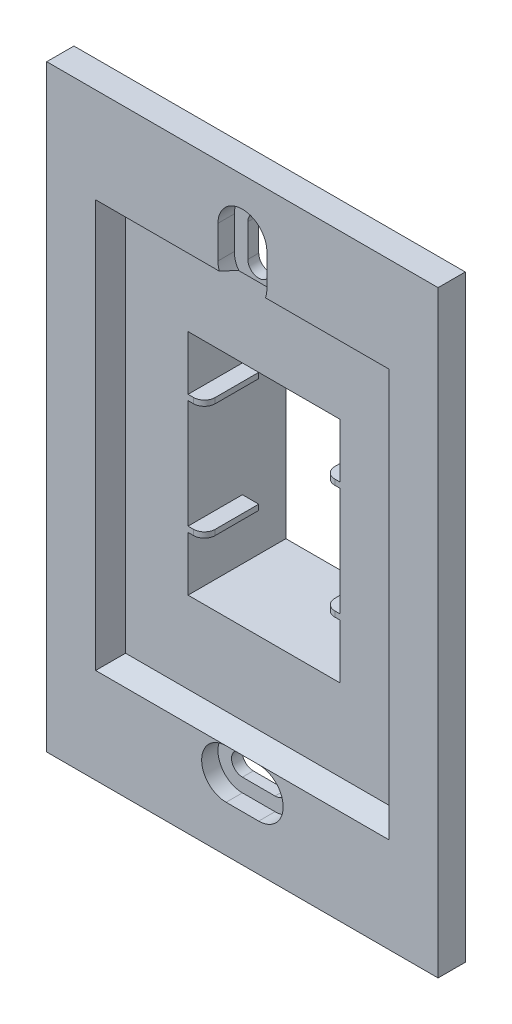
SolidWorks part; units mm, degrees
ref_plane "Plano frontal" through (0, 0, 0) normal (0, 0, 1) x (1, 0, 0)
ref_plane "Plano superior" through (0, 0, 0) normal (0, 1, 0) x (1, 0, 0)
ref_plane "Plano direito" through (0, 0, 0) normal (1, 0, 0) x (0, 0, -1)
sketch "Esboço1" plane through (0, 0, 0) normal (0, 0, 1) x (1, 0, 0)
  line L1 (-36, -55) -> (36, -55)
  line L2 (-36, -55) -> (-36, 55)
  line L3 (-36, 55) -> (36, 55)
  line L4 (36, -55) -> (36, 55)
  line L5 (-36, -55) -> (36, 55) construction
  line L6 (-36, 55) -> (36, -55) construction
  point P0 (0, 0)
  dimension "D1" = 72
  dimension "D2" = 110
extrude "Ressalto-extrusão1" add sketch "Esboço1" along normal blind 5
sketch "Esboço2" plane through (0, 0, 5) normal (0, 0, 1) x (1, 0, 0)
  line L1 (-25.5, -36) -> (25.5, -36)
  line L2 (-25.5, -36) -> (-25.5, 36)
  line L3 (-25.5, 36) -> (25.5, 36)
  line L4 (25.5, -36) -> (25.5, 36)
  line L5 (-25.5, -36) -> (25.5, 36) construction
  line L6 (-25.5, 36) -> (25.5, -36) construction
  point P0 (0, 0)
  dimension "D1" = 51
  dimension "D2" = 72
extrude "Corte-extrusão1" cut sketch "Esboço2" against normal blind 4
chamfer "Chanfro1" distance 1.5 distance2 4 4 edges at (0, -36, 5) (-25.5, 0, 5) (25.5, 0, 5) (0, 36, 5) first distance on face at (0, 0, 5)
sketch "Esboço3" plane through (0, 0, 5) normal (0, 0, 1) x (1, 0, 0)
  line L0 (-2, 45) -> (-2, 39)
  line L1 (2, 45) -> (2, 39)
  arc A2 (2, 45) -> (-2, 45) centre (0, 45) ccw
  arc A3 (-2, 39) -> (2, 39) centre (0, 39) ccw
  point P1 (2, 42)
  dimension "D1" = 4
  dimension "D2" = 4
  dimension "D3" = 6
  dimension "D4" = 42
extrude "Corte-extrusão2" cut sketch "Esboço3" against normal through all
sketch "Esboço4" plane through (0, 0, 5) normal (0, 0, 1) x (1, 0, 0)
  line L0 (-3, -40) -> (3, -40)
  line L1 (-3, -44) -> (3, -44)
  arc A0 (-3, -40) -> (-3, -44) centre (-3, -42) ccw
  arc A1 (3, -44) -> (3, -40) centre (3, -42) ccw
  dimension "D1" = 4
  dimension "D2" = 4
  dimension "D3" = 6
  dimension "D4" = 42
  dimension "D5" = 3
extrude "Corte-extrusão3" cut sketch "Esboço4" against normal through all
sketch "Esboço5" plane through (0, 0, 5) normal (0, 0, 1) x (1, 0, 0)
  line L13 (4.5, 39) -> (4.5, 45)
  line L14 (-4.5, 45) -> (-4.5, 39)
  line L15 (4.5, 39) -> (4.5, 45)
  line L16 (-4.5, 45) -> (-4.5, 39)
  arc A15 (-2.9765, 35.625) -> (2.9765, 35.625) centre (0, 39) ccw
  arc A16 (-4.5, 39) -> (-2.9765, 35.625) centre (0, 39) ccw
  arc A17 (2.9765, 35.625) -> (4.5, 39) centre (0, 39) ccw
  arc A18 (4.5, 45) -> (-4.5, 45) centre (0, 45) ccw
  arc A19 (-2.9765, 35.625) -> (2.9765, 35.625) centre (0, 39) ccw
  arc A20 (-4.5, 39) -> (-2.9765, 35.625) centre (0, 39) ccw
  arc A21 (2.9765, 35.625) -> (4.5, 39) centre (0, 39) ccw
  arc A22 (4.5, 45) -> (-4.5, 45) centre (0, 45) ccw
  dimension "D1" = 2.5
extrude "Corte-extrusão4" cut sketch "Esboço5" against normal blind 3
sketch "Esboço6" plane through (0, 0, 5) normal (0, 0, 1) x (1, 0, 0)
  line L6 (-3, -46.5) -> (3, -46.5)
  line L7 (3, -37.5) -> (-3, -37.5)
  line L8 (-3, -46.5) -> (3, -46.5)
  line L9 (3, -37.5) -> (-3, -37.5)
  arc A8 (3, -46.5) -> (3, -37.5) centre (3, -42) ccw
  arc A9 (-3, -37.5) -> (-3, -46.5) centre (-3, -42) ccw
  arc A10 (3, -46.5) -> (3, -37.5) centre (3, -42) ccw
  arc A11 (-3, -37.5) -> (-3, -46.5) centre (-3, -42) ccw
  dimension "D1" = 2.5
extrude "Corte-extrusão5" cut sketch "Esboço6" against normal blind 3
sketch "Esboço7" plane through (0, 0, 0) normal (0, 0, -1) x (-1, 0, 0)
  line L1 (-15.5, -22) -> (15.5, -22)
  line L2 (-15.5, -22) -> (-15.5, 22)
  line L3 (-15.5, 22) -> (15.5, 22)
  line L4 (15.5, -22) -> (15.5, 22)
  line L5 (-15.5, -22) -> (15.5, 22) construction
  line L6 (-15.5, 22) -> (15.5, -22) construction
  point P0 (0, 0)
  dimension "D1" = 31
  dimension "D2" = 44
extrude "Ressalto-extrusão2" add sketch "Esboço7" along normal blind 17
sketch "Esboço8" plane through (0, 0, -17) normal (0, 0, -1) x (-1, 0, 0)
  line L1 (-14, -21) -> (14, -21)
  line L2 (-14, -21) -> (-14, 21)
  line L3 (-14, 21) -> (14, 21)
  line L4 (14, -21) -> (14, 21)
  line L5 (-14, -21) -> (14, 21) construction
  line L6 (-14, 21) -> (14, -21) construction
  point P0 (0, 0)
  dimension "D1" = 28
  dimension "D2" = 42
extrude "Corte-extrusão6" cut sketch "Esboço8" against normal through all
sketch "Esboço9" plane through (0, 0, 1) normal (0, 0, 1) x (1, 0, 0)
  line L0 (-14, -21) -> (-14, 21) construction
  line L1 (-14, 11) -> (-11, 11)
  line L2 (-14, 11) -> (-14, 10)
  line L3 (-14, 10) -> (-11, 10)
  line L4 (-11, 11) -> (-11, 10)
  line L5 (0, 21) -> (0, -21) construction
  line L6 (-14, 21) -> (14, 21) construction
  line L7 (14, -21) -> (-14, -21) construction
  line L8 (-14, 0) -> (14, 0) construction
  line L9 (14, 21) -> (14, -21) construction
  line L10 (11, 11) -> (11, 10)
  line L11 (14, 10) -> (11, 10)
  line L12 (14, 11) -> (14, 10)
  line L13 (14, 11) -> (11, 11)
  line L14 (14, -11) -> (11, -11)
  line L15 (14, -11) -> (14, -10)
  line L16 (14, -10) -> (11, -10)
  line L17 (11, -11) -> (11, -10)
  line L18 (-11, -11) -> (-11, -10)
  line L19 (-14, -10) -> (-11, -10)
  line L20 (-14, -11) -> (-14, -10)
  line L21 (-14, -11) -> (-11, -11)
  dimension "D1" = 1
  dimension "D2" = 10
  dimension "D3" = 3
extrude "Ressalto-extrusão3" add sketch "Esboço9" against normal blind 10
fillet "Filete1" radius 2 4 edges at (-11, -10.5, 1) (11, -10.5, 1) (11, 10.5, 1) (-11, 10.5, 1)
